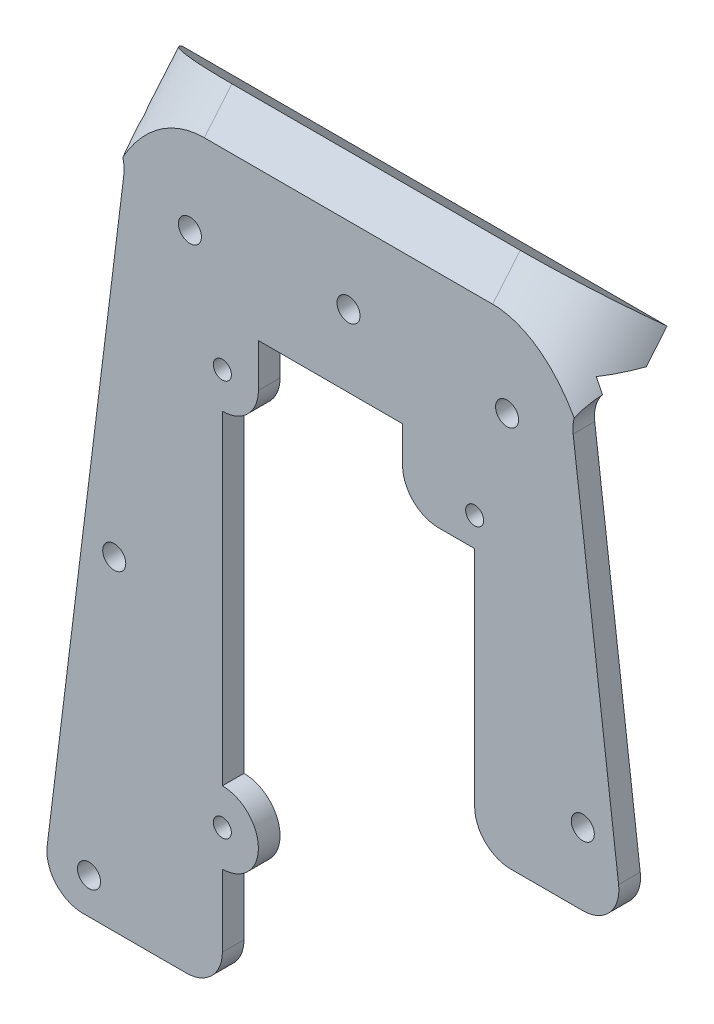
SolidWorks part; units mm, degrees
ref_plane "前视基准面" through (0, 0, 0) normal (0, 0, 1) x (1, 0, 0)
ref_plane "上视基准面" through (0, 0, 0) normal (0, 1, 0) x (1, 0, 0)
ref_plane "右视基准面" through (0, 0, 0) normal (1, 0, 0) x (0, 0, -1)
other "Configuration Table"
sketch "草图1" plane through (0, 0, 0) normal (0, 0, 1) x (1, 0, 0)
  line L0 (0, 0) -> (0, 69.8226) construction
  line L1 (-32.5, 0) -> (32.5, 0) construction
  line L3 (-30, 56) -> (30, 56)
  line L4 (-30, 56) -> (-42.5, -45)
  line L5 (-42.5, -45) -> (42.5, -45)
  line L6 (30, 56) -> (42.5, -45)
  circle A0 centre (-32.5, 0) radius 1.6
  circle A1 centre (32.5, 0) radius 1.6
  circle A2 centre (-22, 44.5) radius 1.6
  circle A3 centre (22, 44.5) radius 1.6
  circle A4 centre (0, 46) radius 1.6
  circle A5 centre (-36, -40) radius 1.6
  point P17 (-46.3454, -47.6982)
  dimension "D2" = 3.2
  dimension "D3" = 22
  dimension "D4" = 44.5
  dimension "D5" = 1.5
  dimension "D7" = 36
  dimension "D11" = 10
  dimension "D1" = 32.5
  dimension "D6" = 40
  dimension "D8" = 45
  dimension "D9" = 85
  dimension "D10" = 60
extrude "凸台-拉伸1" add sketch "草图1" along normal blind 3
sketch "草图2" plane through (0, 0, 3) normal (0, 0, 1) x (1, 0, 0)
  line L1 (42.5, -45) -> (12.5, -45)
  line L2 (42.5, -45) -> (42.5, -10)
  line L3 (42.5, -10) -> (12.5, -10)
  line L4 (12.5, -45) -> (12.5, -10)
  dimension "D1" = 30
  dimension "D2" = 35
extrude "切除-拉伸1" cut sketch "草图2" against normal up to next
sketch "草图3" plane through (0, 0, 3) normal (0, 0, 1) x (1, 0, 0)
  line L0 (0, 56) -> (0, 26) construction
  line L1 (-17.5, 26) -> (17.5, 26)
  line L2 (-17.5, 26) -> (-17.5, -29)
  line L3 (-17.5, -29) -> (17.5, -29)
  line L4 (17.5, 26) -> (17.5, -29)
  line L5 (30, 56) -> (-30, 56) construction
  point P4 (0, 24.2853)
  dimension "D1" = 35
  dimension "D2" = 55
  dimension "D3" = 30
extrude "切除-拉伸2" cut sketch "草图3" against normal up to next
sketch "草图4" plane through (0, 0, 3) normal (0, 0, 1) x (1, 0, 0)
  line L7 (-17.5, 26) -> (7.5, 26)
  line L8 (-17.5, 26) -> (-17.5, 36)
  line L9 (-17.5, 36) -> (7.5, 36)
  line L10 (7.5, 26) -> (7.5, 36)
  dimension "D1" = 25
  dimension "D2" = 10
extrude "切除-拉伸3" cut sketch "草图4" against normal up to next
sketch "草图5" plane through (0, 0, 0) normal (1, 0, 0) x (0, 0, -1)
  line L0 (0, 56) -> (-3, 58.5173)
  line L1 (-3, 58.5173) -> (-3, 56)
  line L2 (-3, 56) -> (0, 56)
  line L3 (-3, -10) -> (-3, 56) construction
  dimension "D1" = 40
extrude "凸台-拉伸2" add sketch "草图5" along normal up to surface and the other way up to surface up to face at (34.0842, 23, 1.5) other way up to face at (-36.25, 5.5, 1.5)
sketch "草图6" plane through (0, 0, 0) normal (1, 0, 0) x (0, 0, -1)
  line L0 (-3, 58.5173) -> (-3, 64.3916)
  line L1 (-3, 64.3916) -> (7.553, 55.5366)
  line L2 (7.553, 55.5366) -> (4.6604, 52.0894)
  line L3 (4.6604, 52.0894) -> (-3, 58.5173) construction
  line L4 (-3, 58.5173) -> (0, 56) construction
  line L5 (4.6604, 52.0894) -> (-3, 52.0894)
  line L6 (-3, -10) -> (-3, 58.5173) construction
  line L7 (-3, 52.0894) -> (-3, 58.5173)
  point P3 (4.6604, 52.0894)
  dimension "D1" = 4.5
  dimension "D2" = 10
extrude "凸台-拉伸3" add sketch "草图6" along normal blind 35 and the other way blind 35
fillet "圆角1" radius 5 2 edges at (-30.484, 52.0894, 1.5) (30.484, 52.0894, 1.5)
sketch "草图8" plane through (0, 36.3093, -30.4672) normal (0, 0.766, -0.6428) x (1, 0, 0)
  line L0 (35, -29.9123) -> (35, -43.6883) construction
  line L1 (-35, -43.6883) -> (35, -43.6883)
  line L2 (-35, -43.6883) -> (-35, -38.6883)
  line L3 (-35, -38.6883) -> (35, -38.6883)
  line L4 (35, -43.6883) -> (35, -38.6883)
  dimension "D1" = 5
extrude "切除-拉伸5" cut sketch "草图8" against normal up to next
sketch "草图7" plane through (0, 36.3093, -30.4672) normal (0, 0.766, -0.6428) x (1, 0, 0)
  line L0 (-35, -43.6883) -> (35, -43.6883) construction
  line L1 (-35, -29.9123) -> (-35, -38.6883) construction
  line L2 (-35, -23.6883) -> (-35, -38.6883)
  line L3 (-35, -38.6883) -> (-20, -38.6883)
  line L4 (0, -29.9123) -> (0, -43.6883) construction
  line L5 (-35, -29.9123) -> (35, -29.9123) construction
  line L6 (35, -38.6883) -> (20, -38.6883)
  line L7 (35, -23.6883) -> (35, -38.6883)
  line L8 (35, -38.6883) -> (-35, -38.6883) construction
  arc A0 (-35, -23.6883) -> (-20, -38.6883) centre (-20, -23.6883) ccw
  arc A1 (35, -23.6883) -> (20, -38.6883) centre (20, -23.6883) cw
  point P2 (-20, -28.6883)
  point P9 (-20, -38.6883)
  point P18 (0, 0)
  dimension "D1" = 30
extrude "切除-拉伸4" cut sketch "草图7" against normal up to next
sketch "草图9" plane through (0, -29, 0) normal (0, 1, 0) x (1, 0, 0)
  line L4 (12.5, 0) -> (-17.5, 0)
  line L5 (-17.5, 0) -> (-17.5, -3)
  line L6 (-17.5, -3) -> (12.5, -3)
  line L7 (12.5, -3) -> (12.5, 0)
  line L8 (12.5, 0) -> (-17.5, 0)
  line L9 (-17.5, 0) -> (-17.5, -3)
  line L10 (-17.5, -3) -> (12.5, -3)
  line L11 (12.5, -3) -> (12.5, 0)
  dimension "D1" = 0
extrude "切除-拉伸6" cut sketch "草图9" against normal up to next
fillet "圆角2" radius 5 5 edges at (-42.5, -45, 1.5) (38.1683, -10, 1.5) (17.5, -10, 1.5) (-17.5, -45, 1.5) (7.5, 26, 1.5)
sketch "草图10" plane through (0, 0, 3) normal (0, 0, 1) x (1, 0, 0)
  line L0 (0, 56.613) -> (0, 0) construction
  line L1 (20, 56.613) -> (-20, 56.613) construction
  line L2 (17.5, 30) -> (-17.5, 30) construction
  line L3 (-17.5, 30) -> (-17.5, -25) construction
  circle A0 centre (17.5, 30) radius 1.25
  circle A1 centre (-17.5, 30) radius 1.25
  circle A2 centre (-17.5, -25) radius 1.25
  dimension "D1" = 35
  dimension "D2" = 2.5
  dimension "D3" = 30
  dimension "D4" = 55
extrude "切除-拉伸7" cut sketch "草图10" against normal up to next
sketch "草图11" plane through (0, 0, 3) normal (0, 0, 1) x (1, 0, 0)
  line L0 (-12.5, 30) -> (-12.5, 36)
  line L1 (7.5, 36) -> (-17.5, 36) construction
  line L2 (-12.5, 36) -> (-17.5, 36)
  line L3 (-17.5, 36) -> (-17.5, 35)
  arc A0 (-17.5, 35) -> (-12.5, 30) centre (-17.5, 30) ccw
  circle A1 centre (-17.5, 30) radius 1.25
  circle A2 centre (-17.5, -25) radius 1.25
  circle A3 centre (-17.5, -25) radius 5
  point P17 (0, 0)
  dimension "D1" = 10
  dimension "D2" = 10
extrude "凸台-拉伸4" add sketch "草图11" against normal up to surface (3 mm away) up to face at (18.75, 30, 0)
